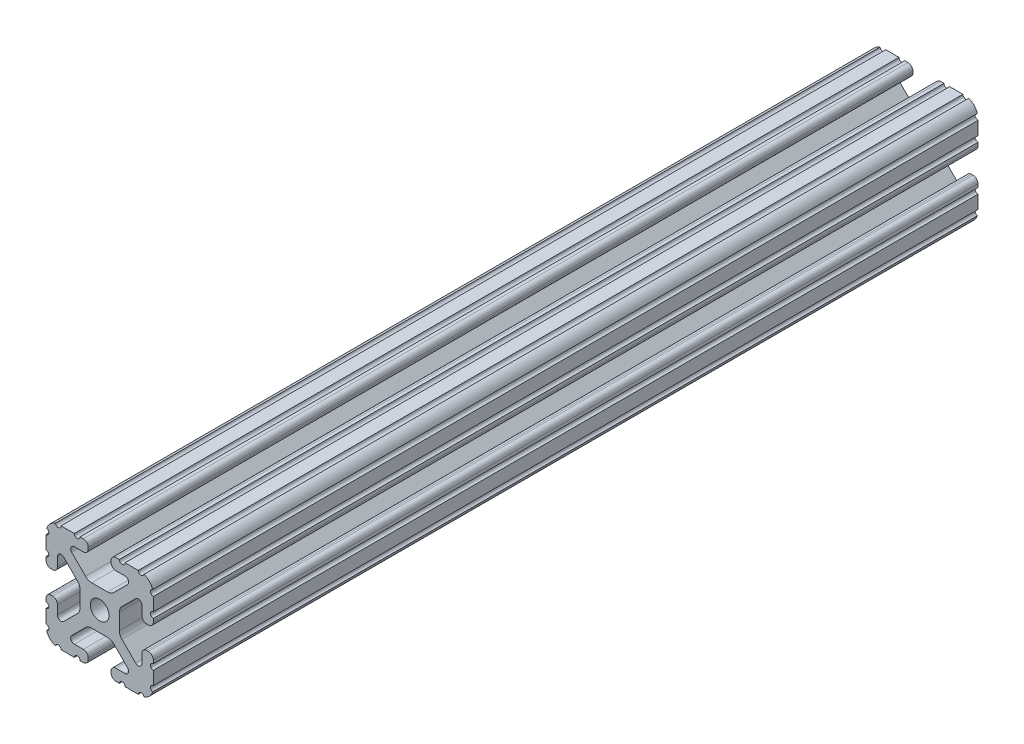
SolidWorks part; units mm, degrees
ref_plane "Front Plane" through (0, 0, 0) normal (0, 0, 1) x (1, 0, 0)
ref_plane "Top Plane" through (0, 0, 0) normal (0, 1, 0) x (1, 0, 0)
ref_plane "Right Plane" through (0, 0, 0) normal (1, 0, 0) x (0, 0, -1)
sketch "Sketch2" plane through (0, 0, 0) normal (0, 0, 1) x (1, 0, 0)
  line L0 (0, 19.05) -> (0, -19.05) construction
  line L1 (-19.05, 0) -> (19.05, 0) construction
  line L2 (4.064, -19.05) -> (19.05, -19.05)
  line L3 (19.05, -19.05) -> (19.05, -4.064)
  line L4 (4.064, -19.05) -> (4.064, -14.986)
  line L5 (4.064, -14.986) -> (12.1123, -14.986)
  line L6 (12.1123, -14.986) -> (4.1113, -6.985)
  line L7 (0, 0) -> (19.05, -19.05) construction
  line L8 (19.05, -4.064) -> (14.986, -4.064)
  line L9 (14.986, -4.064) -> (14.986, -12.1123)
  line L10 (14.986, -12.1123) -> (6.985, -4.1113)
  circle A0 centre (0, 0) radius 3.3274
  arc A1 (8.9963, -14.986) -> (9.909, -12.7826) centre (8.9963, -13.6953) ccw construction
  point P8 (0, -6.985)
  dimension "Center Hole Diameter" = 6.6548
  dimension "Rail Height" = 38.1
  dimension "Rail Width" = 38.1
  dimension "T-Slot Width" = 8.128
  dimension "Slot Inner Width" = 20.574
  dimension "Thickness" = 4.064
  dimension "Slot Depth" = 8.001
  dimension "D1" = 4.064
sketch "Sketch3" plane through (0, 0, 0) normal (1, 0, 0) x (0, 0, -1)
  line L0 (-146.415, -19.05) -> (146.415, -19.05) construction
  line L1 (-121.015, 0) -> (121.015, 0) construction
  dimension "Length" = 292.83
  dimension "D1" = 25.4
sketch "Sketch4" plane through (0, 0, 0) normal (0, 0, 1) x (1, 0, 0)
  line L0 (5.7912, -19.05) -> (14.3002, -19.05)
  line L1 (4.064, -19.05) -> (19.05, -19.05) construction
  line L2 (4.064, -19.05) -> (4.064, -14.986) construction
  line L3 (4.064, -14.986) -> (12.1123, -14.986) construction
  line L4 (4.064, -16.7132) -> (4.064, -17.3228)
  line L5 (5.7912, -14.986) -> (8.9963, -14.986)
  line L6 (0, -6.985) -> (2.833, -6.985)
  line L7 (12.1123, -14.986) -> (4.1113, -6.985) construction
  line L8 (5.0152, -7.8889) -> (9.909, -12.7826)
  line L9 (19.05, -19.05) -> (19.05, -4.064) construction
  line L10 (14.986, -12.1123) -> (6.985, -4.1113) construction
  line L11 (14.986, -4.064) -> (14.986, -12.1123) construction
  line L12 (14.986, -8.9963) -> (14.986, -5.7912)
  line L13 (19.05, -4.064) -> (14.986, -4.064) construction
  line L14 (16.7132, -4.064) -> (17.3228, -4.064)
  line L15 (19.05, -5.7912) -> (19.05, -14.3002)
  line L16 (12.7826, -9.909) -> (7.8889, -5.0152)
  line L17 (6.985, 0) -> (6.985, -2.833)
  line L18 (-19.05, 0) -> (19.05, 0) construction
  line L19 (0, -6.985) -> (0, -3.3274)
  line L20 (0, 19.05) -> (0, -19.05) construction
  line L21 (6.985, 0) -> (3.3274, 0)
  arc A0 (4.064, -17.3228) -> (5.7912, -19.05) centre (5.7912, -17.3228) ccw
  arc A2 (4.064, -16.7132) -> (5.7912, -14.986) centre (5.7912, -16.7132) cw
  arc A3 (8.9963, -14.986) -> (9.909, -12.7826) centre (8.9963, -13.6953) ccw
  arc A4 (2.833, -6.985) -> (5.0152, -7.8889) centre (2.833, -10.0711) cw
  arc A5 (14.3002, -19.05) -> (19.05, -14.3002) centre (14.3002, -14.3002) ccw
  arc A6 (12.7826, -9.909) -> (14.986, -8.9963) centre (13.6953, -8.9963) ccw
  arc A7 (14.986, -5.7912) -> (16.7132, -4.064) centre (16.7132, -5.7912) cw
  arc A8 (17.3228, -4.064) -> (19.05, -5.7912) centre (17.3228, -5.7912) cw
  arc A9 (7.8889, -5.0152) -> (6.985, -2.833) centre (10.0711, -2.833) cw
  circle A10 centre (0, 0) radius 3.3274 construction
  arc A11 (0, -3.3274) -> (3.3274, 0) centre (0, 0) ccw
  dimension "D1" = 4.7498
  dimension "D2" = 3.0861
  dimension "D3" = 1.7272
extrude "Boss-Extrude1" add sketch "Sketch4" along normal mid plane 292.83
sketch "Sketch5" plane through (0, 0, 0) normal (0, 0, 1) x (1, 0, 0)
  line L0 (4.064, -19.05) -> (19.05, -19.05) construction
  line L1 (5.7912, -14.986) -> (8.9963, -14.986) construction
  line L3 (0, 0) -> (19.05, -19.05) construction
  line L4 (8.9963, -14.986) -> (8.9963, -19.05) construction
  line L5 (12.1123, -14.986) -> (4.1113, -6.985) construction
  circle A0 centre (14.7395, -19.05) radius 1.016
  circle A1 centre (7.9803, -19.05) radius 1.016
  circle A2 centre (19.05, -14.7395) radius 1.016
  circle A3 centre (19.05, -7.9803) radius 1.016
  point P10 (7.3938, -14.986)
  point P12 (13.6953, -8.9963)
  dimension "D1" = 2.032
extrude "Cut-Extrude1" cut sketch "Sketch5" against normal through all both and the other way through all
mirror "Mirror1" about plane through (0, 0, 0) normal (1, 0, 0) of bodies 137 134
mirror "Mirror2" about plane through (0, 0, 0) normal (0, 1, 0) of bodies 135
equation "\"D1@Boss-Extrude1\"=\"Length@Sketch3\""
equation "\"D1@Sketch2\"=\"Thickness@Sketch2\""
equation "\"D2@Sketch4\"=\"Slot Inner Width@Sketch2\"*0.15"
equation "\"D1@Sketch4\"=\"D3@Sketch4\"*2.75"
equation "\"D3@Sketch4\"=\"Thickness@Sketch2\"*0.425"
equation "\"D1@Sketch5\"=\"Thickness@Sketch2\"*0.5"
